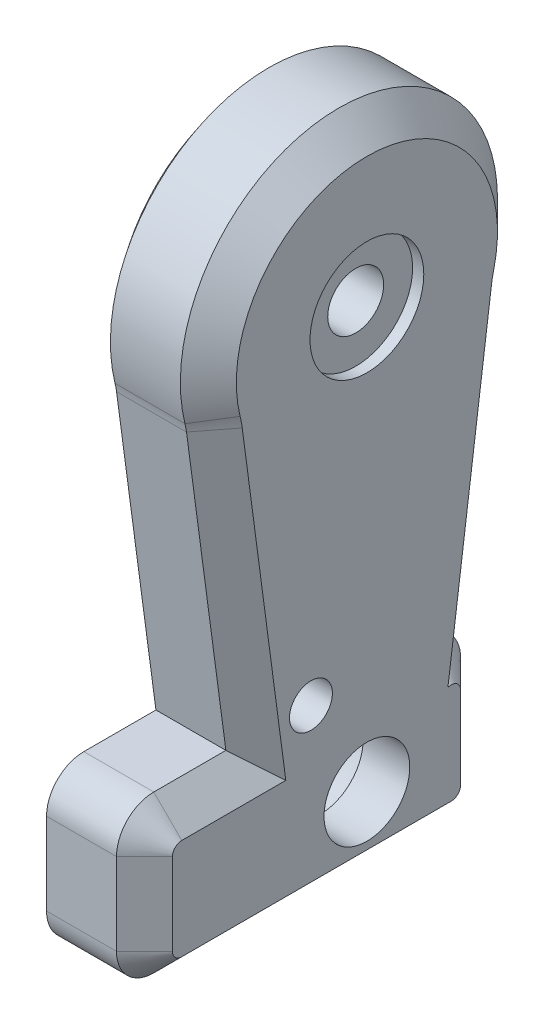
SolidWorks part; units mm, degrees
ref_plane "Front Plane" through (0, 0, 0) normal (0, 0, 1) x (1, 0, 0)
ref_plane "Top Plane" through (0, 0, 0) normal (0, 1, 0) x (1, 0, 0)
ref_plane "Right Plane" through (0, 0, 0) normal (1, 0, 0) x (0, 0, -1)
sketch "Sketch1" plane through (0, 0, 0) normal (1, 0, 0) x (0, 0, -1)
  line L0 (-49.6573, -24.9297) -> (-54.0465, -57.8487)
  line L1 (-52.95, -60.6) -> (-52.95, -69.4)
  line L2 (-56.95, -73.4) -> (-85.85, -73.4)
  line L3 (-89.85, -69.4) -> (-89.85, -60.6)
  line L4 (-85.85, -56.6) -> (-78.12, -56.6)
  line L5 (-78.12, -56.6) -> (-82.3427, -24.9297)
  arc A0 (-82.5053, -24.0712) -> (-49.4947, -24.0712) centre (-66, -20) cw
  arc A1 (-49.4947, -24.0712) -> (-49.6573, -24.9297) centre (-41.7275, -25.987) ccw
  arc A2 (-54.0465, -57.8487) -> (-52.95, -60.6) centre (-56.95, -60.6) cw
  arc A3 (-52.95, -69.4) -> (-56.95, -73.4) centre (-56.95, -69.4) cw
  arc A4 (-85.85, -73.4) -> (-89.85, -69.4) centre (-85.85, -69.4) cw
  arc A5 (-89.85, -60.6) -> (-85.85, -56.6) centre (-85.85, -60.6) cw
  arc A6 (-82.3427, -24.9297) -> (-82.5053, -24.0712) centre (-90.2725, -25.987) ccw
extrude "Boss-Extrude1" add sketch "Sketch1" along normal blind 10.5 from offset 65.9
sketch "Sketch2" plane through (0, 0, 0) normal (1, 0, 0) x (0, 0, -1)
  line L0 (-50.4503, -24.824) -> (-54.8935, -58.1483)
  line L1 (-53.75, -60.6) -> (-53.75, -69.4)
  line L2 (-56.95, -72.6) -> (-85.85, -72.6)
  line L3 (-89.05, -69.4) -> (-89.05, -60.6)
  line L4 (-85.85, -57.4) -> (-77.2063, -57.4)
  line L5 (-77.2063, -57.4) -> (-81.5497, -24.824)
  arc A0 (-81.7286, -23.8796) -> (-50.2714, -23.8796) centre (-66, -20) cw
  arc A1 (-50.2714, -23.8796) -> (-50.4503, -24.824) centre (-41.7275, -25.987) ccw
  arc A2 (-54.8935, -58.1483) -> (-53.75, -60.6) centre (-56.95, -60.6) cw
  arc A3 (-53.75, -69.4) -> (-56.95, -72.6) centre (-56.95, -69.4) cw
  arc A4 (-85.85, -72.6) -> (-89.05, -69.4) centre (-85.85, -69.4) cw
  arc A5 (-89.05, -60.6) -> (-85.85, -57.4) centre (-85.85, -60.6) cw
  arc A6 (-81.5497, -24.824) -> (-81.7286, -23.8796) centre (-90.2725, -25.987) ccw
extrude "Boss-Extrude2" add sketch "Sketch2" along normal blind 0.6 from offset 65.8 separate body
combine bodies "Combine1" operation type subtract main body 101 bodies to subtract 102
chamfer "Chamfer1" distance 3 angle 45 5 edges at (76.4, -41.3892, 51.8519) (76.4, -40.7649, 80.2314) (76.4, -24.4982, 49.5877) (76.4, -24.4982, 82.4123) (76.4, -3, 66)
chamfer "Chamfer2" distance 3 angle 45 8 edges at (76.4, -56.6, 80.4717) (76.4, -57.7716, 88.6784) (76.4, -57.787, 54.1063) (76.4, -65, 89.85) (76.4, -65, 52.95) (76.4, -72.2284, 88.6784) (76.4, -72.2284, 54.1216) (76.4, -73.4, 71.4)
sketch "Sketch3" plane through (0, 0, 0) normal (0, 0, 1) x (1, 0, 0)
  line L1 (65.9, -31.5) -> (68.2, -31.5)
  line L2 (65.9, -31.5) -> (65.9, -8.5)
  line L3 (65.9, -8.5) -> (68.2, -8.5)
  line L4 (68.2, -31.5) -> (68.2, -8.5)
extrude "Boss-Extrude3" add sketch "Sketch3" along normal blind 6.6 from offset 62.7 separate body
combine bodies "Combine2" operation type subtract main body 103 bodies to subtract 104
sketch "Sketch4" plane through (0, 0, 0) normal (0, 0, 1) x (1, 0, 0)
  line L1 (65.9, -23.3) -> (68.2, -23.3)
  line L2 (65.9, -23.3) -> (65.9, -16.7)
  line L3 (65.9, -16.7) -> (68.2, -16.7)
  line L4 (68.2, -23.3) -> (68.2, -16.7)
extrude "Boss-Extrude4" add sketch "Sketch4" along normal blind 23 from offset 54.5 separate body
combine bodies "Combine3" operation type subtract main body 105 bodies to subtract 106
sketch "Sketch5" plane through (0, 0, 0) normal (1, 0, 0) x (0, 0, -1)
  circle A0 centre (-66, -20) radius 4.6
extrude "Boss-Extrude5" add sketch "Sketch5" along normal blind 2.3 from offset 65.9 separate body
combine bodies "Combine4" operation type subtract main body 107 bodies to subtract 108
sketch "Sketch6" plane through (0, 0, 0) normal (1, 0, 0) x (0, 0, -1)
  circle A0 centre (-66, -20) radius 6.1
extrude "Boss-Extrude6" add sketch "Sketch6" along normal blind 1.7 from offset 75.2 separate body
combine bodies "Combine5" operation type subtract main body 109 bodies to subtract 110
sketch "Sketch7" plane through (0, 0, 0) normal (1, 0, 0) x (0, 0, -1)
  circle A0 centre (-66, -20) radius 3
extrude "Boss-Extrude7" add sketch "Sketch7" along normal blind 7.2 from offset 68.1 separate body
combine bodies "Combine6" operation type subtract main body 111 bodies to subtract 112
sketch "Sketch8" plane through (0, 0, 0) normal (0, 0, 1) x (1, 0, 0)
  line L1 (68.1, -14.5) -> (74.2, -14.5)
  line L2 (68.1, -14.5) -> (68.1, -13.4)
  line L3 (68.1, -13.4) -> (74.2, -13.4)
  line L4 (74.2, -14.5) -> (74.2, -13.4)
extrude "Boss-Extrude8" add sketch "Sketch8" along normal blind 1.8 from offset 65.1 separate body
combine bodies "Combine7" operation type subtract main body 113 bodies to subtract 114
sketch "Sketch9" plane through (0, 0, 0) normal (0, 0, 1) x (1, 0, 0)
  line L1 (68.1, -20.9) -> (74.2, -20.9)
  line L2 (68.1, -20.9) -> (68.1, -19.1)
  line L3 (68.1, -19.1) -> (74.2, -19.1)
  line L4 (74.2, -20.9) -> (74.2, -19.1)
extrude "Boss-Extrude9" add sketch "Sketch9" along normal blind 1.1 from offset 71.5 separate body
combine bodies "Combine8" operation type subtract main body 115 bodies to subtract 116
sketch "Sketch10" plane through (0, 0, 0) normal (0, 0, 1) x (1, 0, 0)
  line L1 (68.1, -26.6) -> (74.2, -26.6)
  line L2 (68.1, -26.6) -> (68.1, -25.5)
  line L3 (68.1, -25.5) -> (74.2, -25.5)
  line L4 (74.2, -26.6) -> (74.2, -25.5)
extrude "Boss-Extrude10" add sketch "Sketch10" along normal blind 1.8 from offset 65.1 separate body
combine bodies "Combine9" operation type subtract main body 117 bodies to subtract 118
sketch "Sketch11" plane through (0, 0, 0) normal (0, 0, 1) x (1, 0, 0)
  line L1 (68.1, -20.9) -> (74.2, -20.9)
  line L2 (68.1, -20.9) -> (68.1, -19.1)
  line L3 (68.1, -19.1) -> (74.2, -19.1)
  line L4 (74.2, -20.9) -> (74.2, -19.1)
extrude "Boss-Extrude11" add sketch "Sketch11" along normal blind 1.1 from offset 59.4 separate body
combine bodies "Combine10" operation type subtract main body 119 bodies to subtract 120
sketch "Sketch12" plane through (0, 0, 0) normal (0, 0, 1) x (1, 0, 0)
  line L1 (68.1, -13.4) -> (75.4, -13.4)
  line L2 (68.1, -13.4) -> (68.1, -10)
  line L3 (68.1, -10) -> (75.4, -10)
  line L4 (75.4, -13.4) -> (75.4, -10)
extrude "Boss-Extrude12" add sketch "Sketch12" along normal blind 1.8 from offset 65.1 separate body
combine bodies "Combine11" operation type subtract main body 121 bodies to subtract 122
sketch "Sketch13" plane through (0, 0, 0) normal (0, 0, 1) x (1, 0, 0)
  line L1 (68.1, -20.9) -> (75.4, -20.9)
  line L2 (68.1, -20.9) -> (68.1, -19.1)
  line L3 (68.1, -19.1) -> (75.4, -19.1)
  line L4 (75.4, -20.9) -> (75.4, -19.1)
extrude "Boss-Extrude13" add sketch "Sketch13" along normal blind 3.4 from offset 72.6 separate body
combine bodies "Combine12" operation type subtract main body 123 bodies to subtract 124
sketch "Sketch14" plane through (0, 0, 0) normal (0, 0, 1) x (1, 0, 0)
  line L1 (68.1, -30) -> (75.4, -30)
  line L2 (68.1, -30) -> (68.1, -26.6)
  line L3 (68.1, -26.6) -> (75.4, -26.6)
  line L4 (75.4, -30) -> (75.4, -26.6)
extrude "Boss-Extrude14" add sketch "Sketch14" along normal blind 1.8 from offset 65.1 separate body
combine bodies "Combine13" operation type subtract main body 125 bodies to subtract 126
sketch "Sketch15" plane through (0, 0, 0) normal (0, 0, 1) x (1, 0, 0)
  line L1 (68.1, -20.9) -> (75.4, -20.9)
  line L2 (68.1, -20.9) -> (68.1, -19.1)
  line L3 (68.1, -19.1) -> (75.4, -19.1)
  line L4 (75.4, -20.9) -> (75.4, -19.1)
extrude "Boss-Extrude15" add sketch "Sketch15" along normal blind 3.4 from offset 56 separate body
combine bodies "Combine14" operation type subtract main body 127 bodies to subtract 128
sketch "Sketch16" plane through (0, 0, 0) normal (1, 0, 0) x (0, 0, -1)
  line L0 (-51.9046, -14.8697) -> (-52.4684, -15.0749)
  line L1 (-79.5316, -15.0749) -> (-80.0954, -14.8697)
  arc A0 (-80.0954, -14.8697) -> (-51.9046, -14.8697) centre (-66, -20) cw
  arc A1 (-52.4684, -15.0749) -> (-79.5316, -15.0749) centre (-66, -20) ccw
extrude "Boss-Extrude16" add sketch "Sketch16" along normal blind 2.05 from offset 64.4
sketch "Sketch17" plane through (0, 0, 0) normal (0, 0, 1) x (1, 0, 0)
  line L1 (66.3, -66) -> (70.4, -66)
  line L2 (66.3, -66) -> (66.3, -64)
  line L3 (66.3, -64) -> (70.4, -64)
  line L4 (70.4, -66) -> (70.4, -64)
extrude "Boss-Extrude17" add sketch "Sketch17" along normal blind 2.9 from offset 55.875 separate body
combine bodies "Combine15" operation type subtract main body 130 bodies to subtract 131
sketch "Sketch18" plane through (0, 0, 0) normal (0, 0, 1) x (1, 0, 0)
  line L1 (66.3, -66) -> (70.4, -66)
  line L2 (66.3, -66) -> (66.3, -64)
  line L3 (66.3, -64) -> (70.4, -64)
  line L4 (70.4, -66) -> (70.4, -64)
extrude "Boss-Extrude18" add sketch "Sketch18" along normal blind 2.9 from offset 84.025 separate body
combine bodies "Combine16" operation type subtract main body 132 bodies to subtract 133
sketch "Sketch19" plane through (0, 0, 0) normal (0, 0, 1) x (1, 0, 0)
  line L1 (66.3, -71.5) -> (68.4, -71.5)
  line L2 (66.3, -71.5) -> (66.3, -58.5)
  line L3 (66.3, -58.5) -> (68.4, -58.5)
  line L4 (68.4, -71.5) -> (68.4, -58.5)
extrude "Boss-Extrude19" add sketch "Sketch19" along normal blind 23.4 from offset 59.7 separate body
combine bodies "Combine17" operation type subtract main body 134 bodies to subtract 135
sketch "Sketch20" plane through (0, 0, 0) normal (1, 0, 0) x (0, 0, -1)
  circle A0 centre (-66, -65) radius 6.7
extrude "Boss-Extrude20" add sketch "Sketch20" along normal blind 5.1 from offset 66.3 separate body
combine bodies "Combine18" operation type subtract main body 136 bodies to subtract 137
sketch "Sketch21" plane through (0, 0, 0) normal (1, 0, 0) x (0, 0, -1)
  circle A0 centre (-66, -65) radius 4.6
extrude "Boss-Extrude21" add sketch "Sketch21" along normal blind 5.8 from offset 71.1 separate body
combine bodies "Combine19" operation type subtract main body 138 bodies to subtract 139
sketch "Sketch22" plane through (0, 0, 0) normal (0, 0, 1) x (1, 0, 0)
  line L1 (66.3, -57.8) -> (74.6, -57.8)
  line L2 (66.3, -57.8) -> (66.3, -37)
  line L3 (66.3, -37) -> (74.6, -37)
  line L4 (74.6, -57.8) -> (74.6, -37)
extrude "Boss-Extrude22" add sketch "Sketch22" along normal blind 6 from offset 63 separate body
combine bodies "Combine20" operation type subtract main body 140 bodies to subtract 141
sketch "Sketch23" plane through (0, 0, 0) normal (1, 0, 0) x (0, 0, -1)
  circle A0 centre (-72, -54) radius 2.3
extrude "Boss-Extrude23" add sketch "Sketch23" along normal blind 6 from offset 70.9 separate body
combine bodies "Combine21" operation type subtract main body 142 bodies to subtract 143
sketch "Sketch24" plane through (0, 0, 0) normal (1, 0, 0) x (0, 0, -1)
  circle A0 centre (-72, -54) radius 1.3
extrude "Boss-Extrude24" add sketch "Sketch24" along normal blind 4.65 from offset 66.3 separate body
combine bodies "Combine22" operation type subtract main body 144 bodies to subtract 145
sketch "Sketch25" plane through (0, 0, 0) normal (0, 0, 1) x (1, 0, 0)
  line L1 (66.3, -48.05) -> (70.4, -48.05)
  line L2 (66.3, -48.05) -> (66.3, -43.95)
  line L3 (66.3, -43.95) -> (70.4, -43.95)
  line L4 (70.4, -48.05) -> (70.4, -43.95)
extrude "Boss-Extrude25" add sketch "Sketch25" along normal blind 2.2 from offset 57.4 separate body
combine bodies "Combine23" operation type subtract main body 146 bodies to subtract 147
sketch "Sketch26" plane through (0, 0, 0) normal (0, 1, 0) x (1, 0, 0)
  line L0 (70.6, -59) -> (70.6, -58)
  line L1 (70.6, -58) -> (64.4, -58)
  line L2 (64.4, -58) -> (64.4, -57.6)
  line L3 (64.4, -57.6) -> (63.8, -57.6)
  line L4 (63.8, -57.6) -> (63, -58.4)
  line L5 (63, -58.4) -> (63, -59)
  line L6 (63, -59) -> (70.6, -59)
extrude "Boss-Extrude26" add sketch "Sketch26" along normal blind 3.5 from offset 47.75 offset against normal yes
sketch "Sketch27" plane through (0, 0, 0) normal (0, 0, 1) x (1, 0, 0)
  line L1 (66.3, -48.05) -> (70.4, -48.05)
  line L2 (66.3, -48.05) -> (66.3, -43.95)
  line L3 (66.3, -43.95) -> (70.4, -43.95)
  line L4 (70.4, -48.05) -> (70.4, -43.95)
extrude "Boss-Extrude27" add sketch "Sketch27" along normal blind 2.2 from offset 72.4 separate body
combine bodies "Combine24" operation type subtract main body 149 bodies to subtract 150
sketch "Sketch28" plane through (0, 0, 0) normal (0, 1, 0) x (1, 0, 0)
  line L0 (70.6, -73) -> (70.6, -74)
  line L1 (70.6, -74) -> (64.4, -74)
  line L2 (64.4, -74) -> (64.4, -74.4)
  line L3 (64.4, -74.4) -> (63.8, -74.4)
  line L4 (63.8, -74.4) -> (63, -73.6)
  line L5 (63, -73.6) -> (63, -73)
  line L6 (63, -73) -> (70.6, -73)
extrude "Boss-Extrude28" add sketch "Sketch28" along normal blind 3.5 from offset 47.75 offset against normal yes
